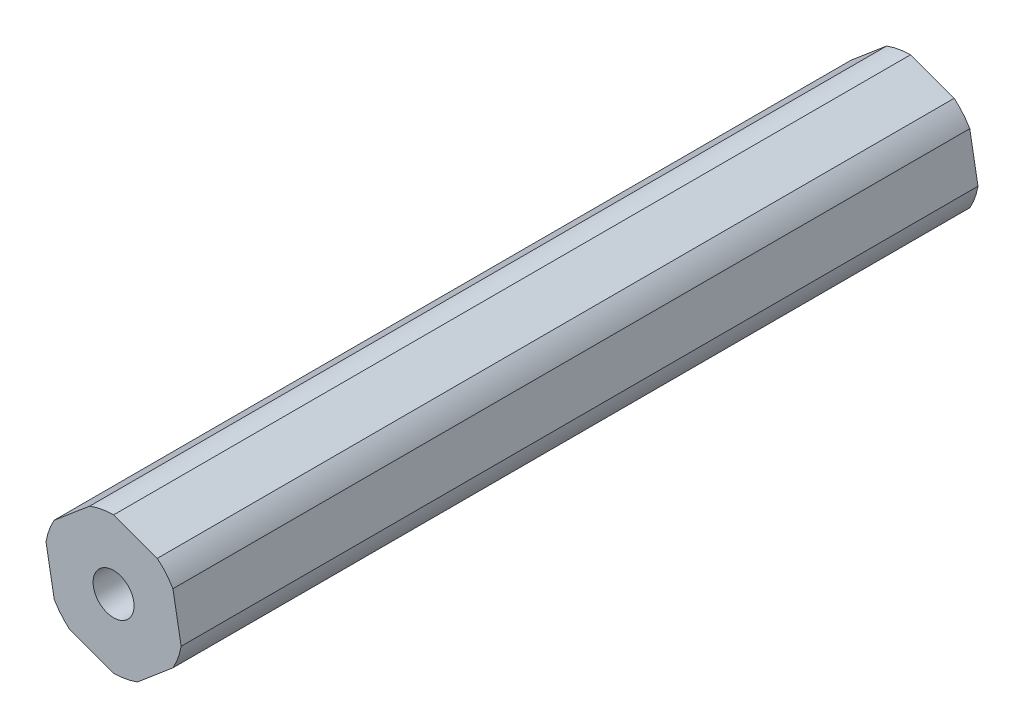
SolidWorks part; units mm, degrees
material "7075-T6 (SN)"
ref_plane "Front Plane" through (0, 0, 0) normal (0, 0, 1) x (1, 0, 0)
ref_plane "Top Plane" through (0, 0, 0) normal (0, 1, 0) x (1, 0, 0)
ref_plane "Right Plane" through (0, 0, 0) normal (1, 0, 0) x (0, 0, -1)
sketch "Sketch1" plane through (0, 0, 0) normal (0, 0, 1) x (1, 0, 0)
  line L1 (-6.6545, 1.1312) -> (-5.8457, -3.375)
  line L2 (-4.3069, -5.1974) -> (0, -6.75)
  line L3 (2.3476, -6.3286) -> (5.8457, -3.375)
  line L4 (6.6545, -1.1312) -> (5.8457, 3.375)
  line L5 (4.3069, 5.1974) -> (0, 6.75)
  line L6 (-2.3476, 6.3286) -> (-5.8457, 3.375)
  circle A0 centre (0, 0) radius 6.35 construction
  arc A1 (-5.8457, 3.375) -> (-6.6545, 1.1312) centre (0, 0) ccw
  arc A2 (-5.8457, -3.375) -> (-4.3069, -5.1974) centre (0, 0) ccw
  arc A3 (0, -6.75) -> (2.3476, -6.3286) centre (0, 0) ccw
  arc A4 (5.8457, -3.375) -> (6.6545, -1.1312) centre (0, 0) ccw
  arc A5 (5.8457, 3.375) -> (4.3069, 5.1974) centre (0, 0) ccw
  arc A6 (0, 6.75) -> (-2.3476, 6.3286) centre (0, 0) ccw
  dimension "D1" = 12.7
  dimension "D2" = 13.5
extrude "Boss-Extrude1" add sketch "Sketch1" along normal blind 78.486
sketch "Sketch2" plane through (0, 0, 78.486) normal (0, 0, 1) x (1, 0, 0)
  circle A0 centre (0, 0) radius 2.0193
  dimension "D1" = 4.0386
extrude "Cut-Extrude1" cut sketch "Sketch2" against normal through all
